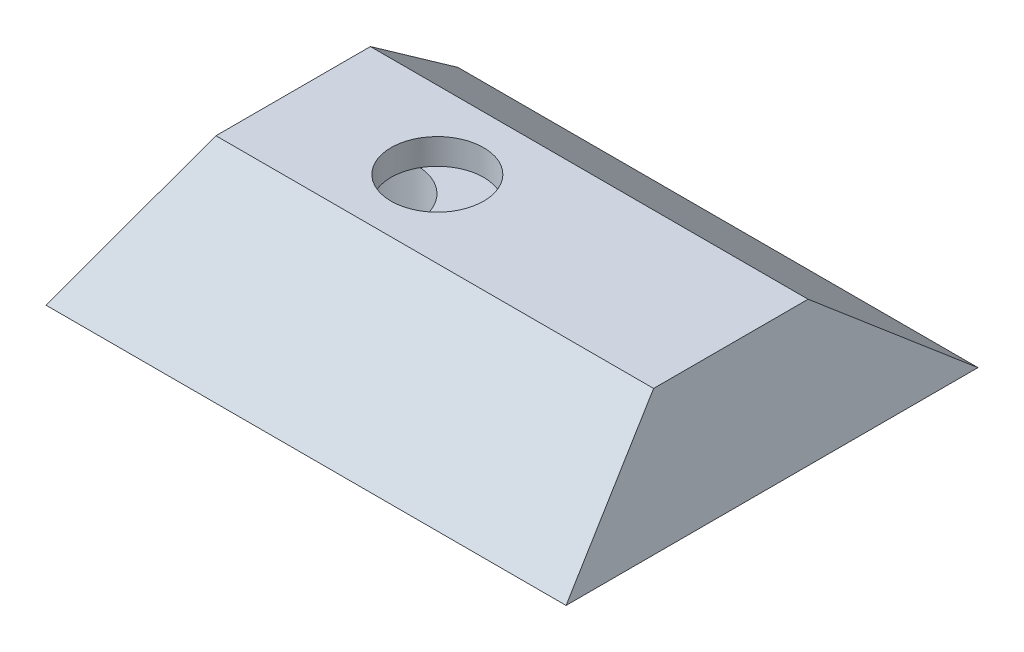
SolidWorks part; units mm, degrees
ref_plane "Front Plane" through (0, 0, 0) normal (0, 0, 1) x (1, 0, 0)
ref_plane "Top Plane" through (0, 0, 0) normal (0, 1, 0) x (1, 0, 0)
ref_plane "Right Plane" through (0, 0, 0) normal (1, 0, 0) x (0, 0, -1)
sketch "Sketch1" plane through (0, 0, 0) normal (0, 1, 0) x (1, 0, 0)
  line L1 (-42.5, 15) -> (42.5, 15)
  line L2 (-42.5, 15) -> (-42.5, -15)
  line L3 (-42.5, -15) -> (42.5, -15)
  line L4 (42.5, 15) -> (42.5, -15)
  line L5 (-42.5, 15) -> (42.5, -15) construction
  line L6 (-42.5, -15) -> (42.5, 15) construction
  point P0 (0, 0)
  dimension "D1" = 85
  dimension "D2" = 30
extrude "Boss-Extrude1" add sketch "Sketch1" along normal blind 20
sketch "Sketch2" plane through (42.5, 0, 0) normal (1, 0, 0) x (0, 0, -1)
  line L0 (15, 20) -> (40, 0)
  line L1 (40, 0) -> (15, 0)
  line L2 (15, 0) -> (15, 20)
  line L3 (-15, 20) -> (-40, 0)
  line L4 (-40, 0) -> (-15, 0)
  line L5 (-15, 0) -> (-15, 20)
  dimension "D1" = 25
  dimension "D2" = 25
extrude "Boss-Extrude2" add sketch "Sketch2" against normal up to surface (85 mm away) up to face at (-42.5, 10, 0)
sketch "Sketch3" plane through (0, 0, 0) normal (0, 0, 1) x (1, 0, 0)
  line L0 (42.5, 20) -> (50.5, 0)
  line L1 (50.5, 0) -> (42.5, 0)
  line L2 (42.5, 0) -> (42.5, 20)
  line L3 (0, 33.8992) -> (0, -24.3108) construction
  line L4 (-42.5, 0) -> (-42.5, 20)
  line L5 (-50.5, 0) -> (-42.5, 0)
  line L6 (-42.5, 20) -> (-50.5, 0)
  dimension "D1" = 8
extrude "Boss-Extrude3" add sketch "Sketch3" against normal up to surface and the other way up to surface up to face at (0, 10, -27.5) other way up to face at (0, 10, 27.5)
sketch "Sketch4" plane through (0, 20, 0) normal (0, 1, 0) x (1, 0, 0)
  line L0 (-44.98, 0) -> (12.5111, 0) construction
  line L1 (-42.5, 15) -> (-42.5, -15) construction
  circle A0 centre (-14.5, 0) radius 3.5
  dimension "D1" = 7
  dimension "D2" = 28
extrude "Cut-Extrude1" cut sketch "Sketch4" against normal through all
sketch "Sketch5" plane through (0, 20, 0) normal (0, 1, 0) x (1, 0, 0)
  circle A0 centre (-14.5, 0) radius 9
  dimension "D1" = 18
extrude "Cut-Extrude2" cut sketch "Sketch5" against normal blind 5
sketch "Sketch6" plane through (0, 0, 0) normal (0, -1, 0) x (1, 0, 0)
  line L0 (-50.5, -40) -> (-50.5, 40) construction
  line L1 (-7.5, -17) -> (-7.5, 5)
  line L2 (-7.5, -17) -> (-31.7768, -22.1612)
  line L3 (-7.5, 5) -> (-32.969, 8.3664)
  line L4 (-9.5, -15.3805) -> (-32.1927, -20.2049)
  line L5 (-9.5, 3.247) -> (-33.231, 6.3836)
  line L6 (-9.5, -15.3805) -> (-9.5, 3.247)
  circle A0 centre (-35, -7) radius 9.5
  circle A1 centre (-14.5, 0) radius 3.5 construction
  circle A2 centre (-14.5, 0) radius 3.5
  arc A3 (-32.969, 8.3664) -> (-31.7768, -22.1612) centre (-35, -7) ccw
  arc A4 (-33.231, 6.3836) -> (-32.1927, -20.2049) centre (-35, -7) ccw
  circle M11 centre (-14.5, 0) radius 3.5
  dimension "D2" = 31
  dimension "D3" = 19
  dimension "D1" = 7
  dimension "D4" = 7
  dimension "D5" = 22
  dimension "D6" = 5
  dimension "D7" = 2
extrude "Boss-Extrude4" add sketch "Sketch6" along normal blind 9 contours L3 A3 L2 L1 A4 L5 L6 L4 region at (-19.7486, 0, -19.0621)
extrude "Cut-Extrude3" cut sketch "Sketch6<3>" against normal blind 7 contours A0 region at (-35, 0, -7)
sketch "Sketch6<3>" plane through (0, 0, 0) normal (0, -1, 0) x (1, 0, 0) same geometry as "Sketch6"
extrude "Boss-Extrude5" add sketch "Sketch6<4>" along normal blind 6 contours L5 A4 L4 L6 A0 M11 region at (-20.945, 0, -17.3287)
sketch "Sketch6<4>" plane through (0, 0, 0) normal (0, -1, 0) x (1, 0, 0) same geometry as "Sketch6"
sketch "Sketch8" plane through (0, -6, 0) normal (0, -1, 0) x (1, 0, 0)
  circle A0 centre (-35, -7) radius 9.5 construction
  circle A1 centre (-35, -7) radius 9.5
  circle A2 centre (-35, -7) radius 10
  dimension "D1" = 20
extrude "Boss-Extrude6" add sketch "Sketch8" along normal blind 13
sketch "Sketch9" plane through (0, 0, 0) normal (1, 0, 0) x (0, 0, -1)
  line L5 (40, 3) -> (-40, 3)
  line L6 (33.8488, 3) -> (-33.8488, 3)
  line L8 (-15, 15) -> (15, 15)
  line L9 (-18.8488, 15) -> (18.8488, 15)
  line L11 (-39.063, -1.1713) -> (-14.063, 18.8287)
  line L12 (-33.8488, 3) -> (-18.8488, 15)
  line L14 (39.063, -1.1713) -> (14.063, 18.8287)
  line L15 (33.8488, 3) -> (18.8488, 15)
  dimension "D1" = 3
  dimension "D2" = 5
  dimension "D3" = 1.5
  dimension "D4" = 1.5
extrude "Cut-Extrude4" cut sketch "Sketch9" against normal blind 40 and the other way blind 5
sketch "Sketch10" plane through (0, 0, 0) normal (0, -1, 0) x (-1, 0, 0)
  line L0 (-8.3542, 25.6797) -> (-8.3542, -20.8667)
  line L1 (-8.3542, 25.6797) -> (-42.9725, 25.6797)
  line L2 (-42.9725, 25.6797) -> (-42.9725, -20.8667)
  line L3 (-8.3542, -20.8667) -> (-42.9725, -20.8667)
  line L4 (50.5, 40) -> (50.5, 7) construction
  dimension "D1" = 58.8542
  dimension "D2" = 93.4725
  dimension "D3" = 30.6797
  dimension "D4" = 15.8667
extrude "Cut-Extrude5" cut sketch "Sketch10" against normal blind 6
